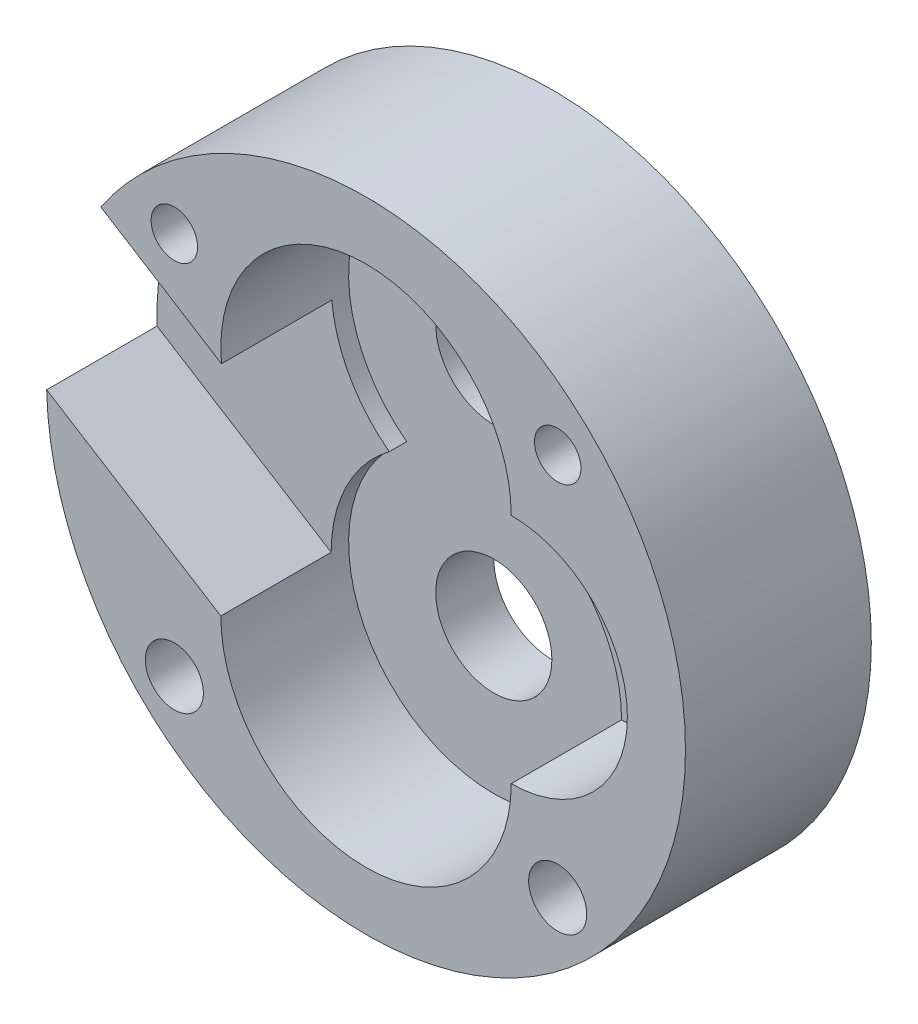
SolidWorks part; units mm, degrees
ref_plane "Front" through (0, 0, 0) normal (0, 0, 1) x (1, 0, 0)
ref_plane "Top" through (0, 0, 0) normal (0, 1, 0) x (1, 0, 0)
ref_plane "Right" through (0, 0, 0) normal (1, 0, 0) x (0, 0, -1)
sketch "Sketch1" plane through (0, 0, 0) normal (0, 0, 1) x (1, 0, 0)
  line L0 (-33, 54.7282) -> (-33, -60.6448) construction
  line L1 (33, 60.1897) -> (33, -60.6448) construction
  line L2 (-55.6021, -33) -> (57.0403, -33) construction
  line L3 (-53.554, 33) -> (57.0403, 33) construction
  line L4 (-54.9855, -1.263) -> (-25, -20)
  line L5 (-45.6688, 30.649) -> (-24.8908, 17.6654)
  line L6 (-78.572, -20) -> (78.572, -20) construction
  circle A0 centre (0, 0) radius 55
  circle A1 centre (0, 20) radius 10
  circle A2 centre (0, -20) radius 10
  arc A3 (15, 0) -> (-15, 0) centre (0, 20) ccw
  arc A4 (-15, 0) -> (15, 0) centre (0, -20) ccw
  arc A5 (25, 20) -> (25, -20) centre (25, 0) cw
  circle A6 centre (-33, 33) radius 4
  circle A7 centre (33, 33) radius 4
  circle A8 centre (33, -33) radius 5
  circle A9 centre (-33, -33) radius 5
  dimension "D1" = 110
  dimension "D2" = 20
  dimension "D3" = 40
  dimension "D4" = 20
  dimension "D5" = 50
  dimension "D6" = 20
  dimension "D12" = 8
  dimension "D13" = 10
  dimension "D7" = 25
  dimension "D8" = 33
  dimension "D9" = 33
  dimension "D10" = 33
  dimension "D11" = 33
  dimension "D14" = 32
  dimension "D15" = 32
extrude "Boss-Extrude1" add sketch "Sketch1" against normal blind 32 contours A0
extrude "Cut-Extrude1" cut sketch "Sketch1<19>" against normal blind 22 contours A3 A4 A2 A1 | A2 | A1 region at (0, 0, 0) region at (0, 20, 0) region at (0, -20, 0)
sketch "Sketch1<19>" plane through (0, 0, 0) normal (0, 0, 1) x (1, 0, 0) same geometry as "Sketch1"
extrude "Cut-Extrude2" cut sketch "Sketch1<20>" against normal blind 19 contours A4 A3 L5 A0 L4 | A5 A3 A4 region at (-36.8252, 5.5729, 0) region at (31.663, 0, 0)
sketch "Sketch1<20>" plane through (0, 0, 0) normal (0, 0, 1) x (1, 0, 0) same geometry as "Sketch1"
extrude "Cut-Extrude3" cut sketch "Sketch1<21>" against normal through all contours A6 | A7 | A8 | A9 | A2 | A1
sketch "Sketch1<21>" plane through (0, 0, 0) normal (0, 0, 1) x (1, 0, 0) same geometry as "Sketch1"
